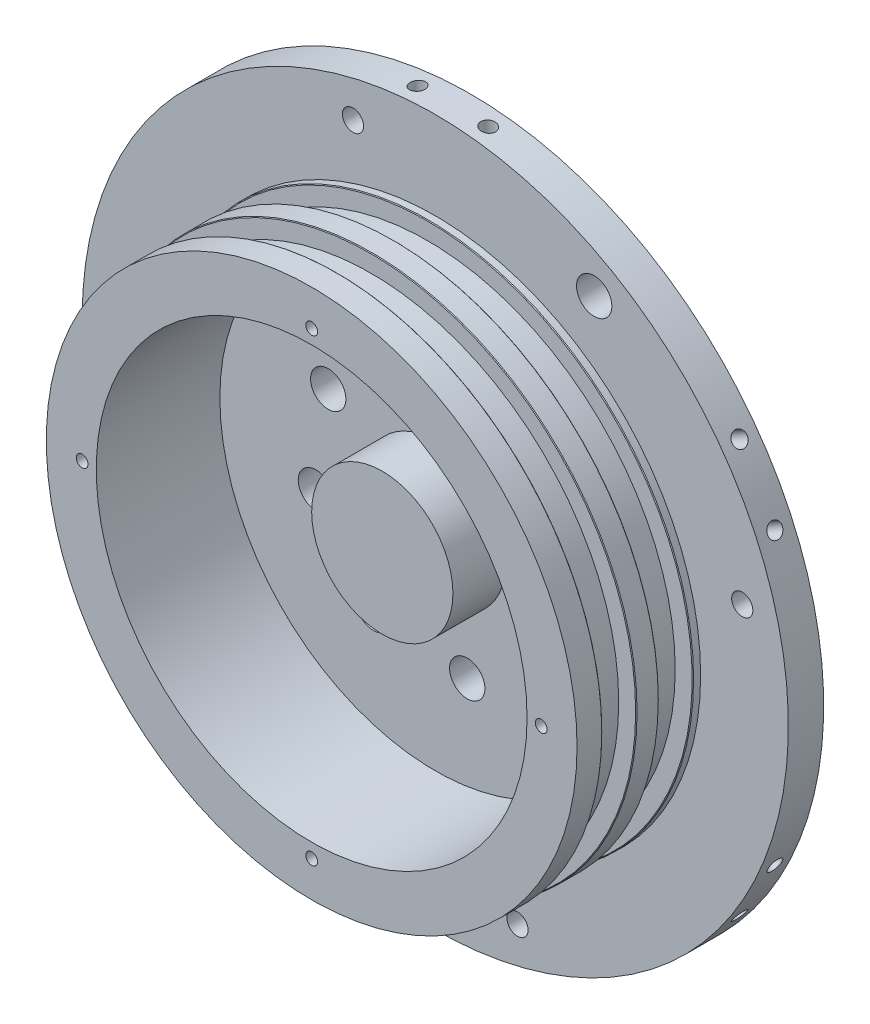
SolidWorks part; units mm, degrees
other "Marquage1"
sketch "Esquisse22" plane through (-100, 100, -114.225) normal (-0.6969, 0.6451, 0.3132) x (0.5706, 0.7634, -0.3027)
sketch "Esquisse26" plane through (-110, 110, -114.225) normal (-0.6969, 0.6451, 0.3132) x (0.5706, 0.7634, -0.3027)
sketch "Esquisse28" plane through (-110, 110, -114.225) normal (-0.6969, 0.6451, 0.3132) x (0.5706, 0.7634, -0.3027)
sketch "Esquisse31" plane through (-110, 110, -114.225) normal (-0.6969, 0.6451, 0.3132) x (0.5706, 0.7634, -0.3027)
sketch "Esquisse32" plane through (-100, 100, -114.225) normal (-0.6969, 0.6451, 0.3132) x (0.5706, 0.7634, -0.3027)
material "AISI 316 Barre d'acier inoxydable recuit (SS)"
ref_plane "Plan de face" through (0, 0, 0) normal (0, 0, 1) x (1, 0, 0)
ref_plane "Plan de dessus" through (0, 0, 0) normal (0, 1, 0) x (1, 0, 0)
ref_plane "Plan de droite" through (0, 0, 0) normal (1, 0, 0) x (0, 0, -1)
sketch "Esquisse1" plane through (0, 0, 0) normal (0, 1, 0) x (1, 0, 0)
  line L0 (87.5, 159.225) -> (0, 159.225)
  line L1 (0, 159.225) -> (0, 114.225)
  line L2 (0, 114.225) -> (75.15, 114.225)
  line L3 (75.15, 114.225) -> (75.15, 121.425)
  line L4 (75.15, 121.425) -> (70.15, 121.425)
  line L5 (70.15, 121.425) -> (70.15, 131.025)
  line L6 (70.15, 131.025) -> (75.15, 131.025)
  line L7 (75.15, 131.025) -> (75.15, 137.425)
  line L8 (75.15, 137.425) -> (70.15, 137.425)
  line L9 (70.15, 137.425) -> (70.15, 147.025)
  line L10 (70.15, 147.025) -> (75.15, 147.025)
  line L11 (75.15, 147.025) -> (75.15, 149.225)
  line L12 (75.15, 149.225) -> (87.5, 149.225)
  line L13 (87.5, 149.225) -> (87.5, 159.225)
  line L14 (0, 159.225) -> (0, 114.225) construction
revolve "Révolution1" add sketch "Esquisse1" angle 360 about L14 reverse direction yes
hole_wizard "Diamètre du perçage Ø9.0 (9)1" positions "Esquisse3" profile "Esquisse2" hole size "Ø9.0" standard "Ansi Metric"
sketch "Esquisse3" plane through (0, 0, -149.225) normal (0, 0, 1) x (1, 0, 0)
  point P0 (-87.5, 0)
  point P1 (0, 87.5)
  point P2 (0, -87.5)
  point P3 (87.5, 0)
sketch "Esquisse2" plane through (-87.5, 0, -149.225) normal (1, 0, 0) x (0, -1, 0)
  line L0 (0, 0) -> (0, 3)
  line L1 (0, 3) -> (4.5, 3)
  line L2 (4.5, 3) -> (4.5, 0)
  line L5 (4.5, 0) -> (0, 0)
  line L10 (0, 3) -> (-4.5, 3) construction
  line L11 (0, -6.35) -> (0, 107.95) construction
  dimension "Diamètre du perçage" = 9
  dimension "Profondeur du perçage" = 3
  dimension "Angle de pointe" = 180
hole_wizard "Dégagement M31" positions "Esquisse5" profile "Esquisse4" hole size "M3" standard "Ansi Metric"
sketch "Esquisse5" plane through (0, 0, -114.225) normal (0, 0, 1) x (1, 0, 0)
  point P0 (-65, 0)
  point P1 (65, 0)
  point P2 (0, 65)
  point P3 (0, -65)
sketch "Esquisse4" plane through (-65, 0, -114.225) normal (1, 0, 0) x (0, -1, 0)
  line L0 (0, 0) -> (0, 17.001)
  line L1 (0, 17.001) -> (1.666, 16)
  line L2 (1.666, 16) -> (1.666, 0)
  line L5 (1.666, 0) -> (0, 0)
  line L10 (0, 17.001) -> (-1.666, 16) construction
  line L11 (0, -6.35) -> (0, 107.95) construction
  dimension "Diamètre du perçage" = 3.332
  dimension "Profondeur du perçage" = 16
  dimension "Angle de pointe" = 118
hole_wizard "Dégagement M1001" positions "Esquisse7" profile "Esquisse6" hole size "M100" standard "Ansi Metric"
sketch "Esquisse7" plane through (0, 0, -114.225) normal (0, 0, 1) x (1, 0, 0)
  point P0 (0, 0)
sketch "Esquisse6" plane through (0, 0, -114.225) normal (1, 0, 0) x (0, -1, 0)
  line L0 (0, 0) -> (0, 35)
  line L1 (0, 35) -> (55, 35)
  line L2 (55, 35) -> (55, 0)
  line L5 (55, 0) -> (0, 0)
  line L10 (0, 35) -> (-55, 35) construction
  line L11 (0, -6.35) -> (0, 107.95) construction
  dimension "Diamètre du perçage" = 110
  dimension "Profondeur du perçage" = 35
  dimension "Angle de pointe" = 180
sketch "Esquisse8" plane through (0, 0, -159.225) normal (0, 0, -1) x (-1, 0, 0)
  line L0 (0, 0) -> (0, -108.9201) construction
  circle A0 centre (0, 0) radius 108.9201 construction
  circle A1 centre (0, 0) radius 100
  circle A2 centre (0, 0) radius 77.5
  circle A3 centre (0, 0) radius 87.5 construction
  dimension "D2" = 10
  dimension "D1" = 200
extrude "Boss.-Extru.1" add sketch "Esquisse8" against normal blind 10
sketch "Esquisse9" plane through (0, 0, -159.225) normal (0, 0, 1) x (1, 0, 0)
  line L0 (0, -65) -> (0, 0) construction
  line L1 (-56.2917, -32.5) -> (0, -65) construction
  line L2 (-56.2917, -32.5) -> (0, 0) construction
  line L3 (0, 0) -> (-28.1458, -48.75) construction
  circle A0 centre (0, -65) radius 2.5
  circle A3 centre (-56.2917, -32.5) radius 2.5
  circle A4 centre (-56.2917, 32.5) radius 2.5
  circle A5 centre (0, 65) radius 2.5
  circle A6 centre (56.2917, 32.5) radius 2.5
  circle A7 centre (56.2917, -32.5) radius 2.5
  point P31 (0, 0)
  dimension "D1" = 5
  dimension "D2" = 65
  dimension "D3" = 6
extrude "Enlèv. mat.-Extru.1" cut sketch "Esquisse9" along normal blind 20
ref_plane "Plan1" through (0, -100, 0) normal (0, -1, 0) x (-1, 0, 0)
sketch "Esquisse10" plane through (0, -100, 0) normal (0, -1, 0) x (1, 0, 0)
  line L0 (0, -159.225) -> (0, -149.225) construction
  line L2 (-100, -159.225) -> (100, -159.225) construction
  line L3 (100, -149.225) -> (-100, -149.225) construction
  circle A3 centre (10, -154.225) radius 2.1
  circle A4 centre (-10, -154.225) radius 2.1
  dimension "D1" = 4.2
  dimension "D2" = 5
  dimension "D3" = 20
extrude "Enlèv. mat.-Extru.2" cut sketch "Esquisse10" against normal blind 25
pattern_circular "Répétition circulaire1" count 6 every 60 about axis through (0, 0, -121.425) along (0, 0, 1) of "Enlèv. mat.-Extru.2"
sketch "Esquisse24" plane through (0, 0, -159.225) normal (0, 0, -1) x (-1, 0, 0)
  line L0 (28.0621, 104.7291) -> (0, 0) construction
  line L1 (-54.2118, 93.8976) -> (0, 0) construction
  line L2 (0, 0) -> (0, 65) construction
  circle A0 centre (-45, 77.9423) radius 5
  circle A1 centre (23.2937, 86.9333) radius 3
  circle A2 centre (86.9333, -23.2937) radius 3
  circle A3 centre (-23.2937, -86.9333) radius 3
  circle A4 centre (-86.9333, 23.2937) radius 3
  circle A5 centre (-17.5, 30.3109) radius 5
  circle A6 centre (9.0587, 33.8074) radius 5
  circle A7 centre (30.3109, 17.5) radius 5
  circle A8 centre (33.8074, -9.0587) radius 5
  circle A9 centre (17.5, -30.3109) radius 5
  circle A10 centre (-9.0587, -33.8074) radius 5
  circle A11 centre (-30.3109, -17.5) radius 5
  circle A12 centre (-33.8074, 9.0587) radius 5
  point P19 (0, 0)
  point P36 (0, 0)
  dimension "D1" = 6
  dimension "D3" = 10
  dimension "D6" = 10
  dimension "D2" = 90
  dimension "D4" = 90
  dimension "D7" = 35
  dimension "D9" = 45
  dimension "D10" = 15
  dimension "D5" = 4
  dimension "D8" = 8
extrude "Enlèv. mat.-Extru.15" cut sketch "Esquisse24" against normal through all and the other way through all
sketch "Esquisse27" plane through (0, 0, -114.225) normal (0, 0, 1) x (1, 0, 0)
  circle A0 centre (0, 0) radius 62.15
  circle A1 centre (0, 0) radius 70.15 construction
  circle A2 centre (0, 0) radius 70.15 construction
  dimension "D1" = 8
chamfer "Chanfrein1" distance 0.2 angle 45 4 edges at (75.15, 0, -147.025) (75.15, 0, -121.425) (75.15, 0, -131.025) (75.15, 0, -137.425)
sketch "Esquisse25" plane through (0, 0, -159.225) normal (0, 0, -1) x (-1, 0, 0)
  line L0 (-31.6901, 0.1056) -> (-40.1175, 2.3637) construction
  line L1 (-40.1175, 2.3637) -> (-35.9247, 18.0117) construction
  line L2 (-35.9247, 18.0117) -> (-27.4973, 15.7536) construction
  line L3 (-27.4973, 15.7536) -> (-31.6901, 0.1056) construction
  line L4 (0, 0) -> (-38.0211, 10.1877) construction
  line L5 (-33.8074, 9.0587) -> (-40.6755, -16.5735) construction
  line L6 (-29.2962, 16.2356) -> (-34.1258, 17.5297)
  line L7 (-33.489, 0.5876) -> (-38.3187, 1.8817)
  line L8 (-9.2352, 32.1958) -> (-11.7352, 36.526)
  line L9 (-23.2648, 24.0958) -> (-25.7648, 28.426)
  line L10 (16.2356, 29.2962) -> (17.5297, 34.1258)
  line L11 (0.5876, 33.489) -> (1.8817, 38.3187)
  line L12 (32.1958, 9.2352) -> (36.526, 11.7352)
  line L13 (24.0958, 23.2648) -> (28.426, 25.7648)
  line L14 (29.2962, -16.2356) -> (34.1258, -17.5297)
  line L15 (33.489, -0.5876) -> (38.3187, -1.8817)
  line L16 (9.2352, -32.1958) -> (11.7352, -36.526)
  line L17 (23.2648, -24.0958) -> (25.7648, -28.426)
  line L18 (-16.2356, -29.2962) -> (-17.5297, -34.1258)
  line L19 (-0.5876, -33.489) -> (-1.8817, -38.3187)
  line L20 (-32.1958, -9.2352) -> (-36.526, -11.7352)
  line L21 (-24.0958, -23.2648) -> (-28.426, -25.7648)
  arc A2 (-40.1175, 2.3637) -> (-35.9247, 18.0117) centre (-33.8074, 9.0587) cw construction
  arc A3 (-31.6901, 0.1056) -> (-27.4973, 15.7536) centre (-33.8074, 9.0587) ccw construction
  arc A4 (-29.5648, 0.8953) -> (-26.0515, 14.007) centre (-33.8074, 9.0587) ccw
  arc A5 (-26.0515, 14.007) -> (-26.2567, 14.3863) centre (-23.5224, 15.6206) cw
  arc A6 (-26.2567, 14.3863) -> (-28.7554, 16.1427) centre (-28.991, 13.1519) ccw
  arc A7 (-28.7554, 16.1427) -> (-29.2962, 16.2356) centre (-28.5197, 19.1334) cw
  arc A8 (-34.6406, 17.7196) -> (-34.1258, 17.5297) centre (-33.3493, 20.4275) ccw
  arc A9 (-37.6827, 17.4479) -> (-34.6406, 17.7196) centre (-35.9319, 15.0117) cw
  arc A10 (-38.05, 17.222) -> (-37.6827, 17.4479) centre (-39.4335, 19.884) ccw
  arc A11 (-41.5633, 4.1103) -> (-38.05, 17.222) centre (-33.8074, 9.0587) cw
  arc A12 (-41.5633, 4.1103) -> (-41.3581, 3.7311) centre (-44.0924, 2.4967) cw
  arc A13 (-41.3581, 3.7311) -> (-38.8594, 1.9747) centre (-38.6238, 4.9654) ccw
  arc A14 (-38.8594, 1.9747) -> (-38.3187, 1.8817) centre (-39.0951, -1.0161) cw
  arc A15 (-32.9742, 0.3977) -> (-33.489, 0.5876) centre (-34.2655, -2.3102) ccw
  arc A16 (-29.9321, 0.6695) -> (-32.9742, 0.3977) centre (-31.6829, 3.1056) cw
  arc A17 (-29.5648, 0.8953) -> (-29.9321, 0.6695) centre (-28.1813, -1.7666) ccw
  arc A19 (-26.4833, 32.2961) -> (-14.7276, 39.0832) centre (-17.5, 30.3109) cw
  arc A20 (-14.7276, 39.0832) -> (-14.3082, 38.9832) centre (-13.8236, 41.9438) ccw
  arc A21 (-14.3082, 38.9832) -> (-11.9649, 37.0243) centre (-14.7928, 36.0226) cw
  arc A22 (-11.9649, 37.0243) -> (-11.7352, 36.526) centre (-9.1371, 38.026) ccw
  arc A23 (-8.9185, 31.7477) -> (-9.2352, 32.1958) centre (-6.6371, 33.6958) cw
  arc A24 (-8.3937, 28.7389) -> (-8.9185, 31.7477) centre (-11.1999, 29.7996) ccw
  arc A25 (-8.5167, 28.3257) -> (-8.3937, 28.7389) centre (-5.5874, 27.6783) cw
  arc A26 (-20.2724, 21.5386) -> (-8.5167, 28.3257) centre (-17.5, 30.3109) ccw
  arc A27 (-20.2724, 21.5386) -> (-20.6918, 21.6386) centre (-21.1764, 18.678) ccw
  arc A28 (-20.6918, 21.6386) -> (-23.0351, 23.5975) centre (-20.2072, 24.5992) cw
  arc A29 (-23.0351, 23.5975) -> (-23.2648, 24.0958) centre (-25.8629, 22.5958) ccw
  arc A30 (-26.0815, 28.8741) -> (-25.7648, 28.426) centre (-28.3629, 26.926) cw
  arc A31 (-26.6063, 31.8828) -> (-26.0815, 28.8741) centre (-23.8001, 30.8222) ccw
  arc A32 (-26.4833, 32.2961) -> (-26.6063, 31.8828) centre (-29.4126, 32.9435) cw
  arc A33 (4.1103, 41.5633) -> (17.222, 38.05) centre (9.0587, 33.8074) cw
  arc A34 (17.222, 38.05) -> (17.4479, 37.6827) centre (19.884, 39.4335) ccw
  arc A35 (17.4479, 37.6827) -> (17.7196, 34.6406) centre (15.0117, 35.9319) cw
  arc A36 (17.7196, 34.6406) -> (17.5297, 34.1258) centre (20.4275, 33.3493) ccw
  arc A37 (16.1427, 28.7554) -> (16.2356, 29.2962) centre (19.1334, 28.5197) cw
  arc A38 (14.3863, 26.2567) -> (16.1427, 28.7554) centre (13.1519, 28.991) ccw
  arc A39 (14.007, 26.0515) -> (14.3863, 26.2567) centre (15.6206, 23.5224) cw
  arc A40 (0.8953, 29.5648) -> (14.007, 26.0515) centre (9.0587, 33.8074) ccw
  arc A41 (0.8953, 29.5648) -> (0.6695, 29.9321) centre (-1.7666, 28.1813) ccw
  arc A42 (0.6695, 29.9321) -> (0.3977, 32.9742) centre (3.1056, 31.6829) cw
  arc A43 (0.3977, 32.9742) -> (0.5876, 33.489) centre (-2.3102, 34.2655) ccw
  arc A44 (1.9747, 38.8594) -> (1.8817, 38.3187) centre (-1.0161, 39.0951) cw
  arc A45 (3.7311, 41.3581) -> (1.9747, 38.8594) centre (4.9654, 38.6238) ccw
  arc A46 (4.1103, 41.5633) -> (3.7311, 41.3581) centre (2.4967, 44.0924) cw
  arc A47 (32.2961, 26.4833) -> (39.0832, 14.7276) centre (30.3109, 17.5) cw
  arc A48 (39.0832, 14.7276) -> (38.9832, 14.3082) centre (41.9438, 13.8236) ccw
  arc A49 (38.9832, 14.3082) -> (37.0243, 11.9649) centre (36.0226, 14.7928) cw
  arc A50 (37.0243, 11.9649) -> (36.526, 11.7352) centre (38.026, 9.1371) ccw
  arc A51 (31.7477, 8.9185) -> (32.1958, 9.2352) centre (33.6958, 6.6371) cw
  arc A52 (28.7389, 8.3937) -> (31.7477, 8.9185) centre (29.7996, 11.1999) ccw
  arc A53 (28.3257, 8.5167) -> (28.7389, 8.3937) centre (27.6783, 5.5874) cw
  arc A54 (21.5386, 20.2724) -> (28.3257, 8.5167) centre (30.3109, 17.5) ccw
  arc A55 (21.5386, 20.2724) -> (21.6386, 20.6918) centre (18.678, 21.1764) ccw
  arc A56 (21.6386, 20.6918) -> (23.5975, 23.0351) centre (24.5992, 20.2072) cw
  arc A57 (23.5975, 23.0351) -> (24.0958, 23.2648) centre (22.5958, 25.8629) ccw
  arc A58 (28.8741, 26.0815) -> (28.426, 25.7648) centre (26.926, 28.3629) cw
  arc A59 (31.8828, 26.6063) -> (28.8741, 26.0815) centre (30.8222, 23.8001) ccw
  arc A60 (32.2961, 26.4833) -> (31.8828, 26.6063) centre (32.9435, 29.4126) cw
  arc A61 (41.5633, -4.1103) -> (38.05, -17.222) centre (33.8074, -9.0587) cw
  arc A62 (38.05, -17.222) -> (37.6827, -17.4479) centre (39.4335, -19.884) ccw
  arc A63 (37.6827, -17.4479) -> (34.6406, -17.7196) centre (35.9319, -15.0117) cw
  arc A64 (34.6406, -17.7196) -> (34.1258, -17.5297) centre (33.3493, -20.4275) ccw
  arc A65 (28.7554, -16.1427) -> (29.2962, -16.2356) centre (28.5197, -19.1334) cw
  arc A66 (26.2567, -14.3863) -> (28.7554, -16.1427) centre (28.991, -13.1519) ccw
  arc A67 (26.0515, -14.007) -> (26.2567, -14.3863) centre (23.5224, -15.6206) cw
  arc A68 (29.5648, -0.8953) -> (26.0515, -14.007) centre (33.8074, -9.0587) ccw
  arc A69 (29.5648, -0.8953) -> (29.9321, -0.6695) centre (28.1813, 1.7666) ccw
  arc A70 (29.9321, -0.6695) -> (32.9742, -0.3977) centre (31.6829, -3.1056) cw
  arc A71 (32.9742, -0.3977) -> (33.489, -0.5876) centre (34.2655, 2.3102) ccw
  arc A72 (38.8594, -1.9747) -> (38.3187, -1.8817) centre (39.0951, 1.0161) cw
  arc A73 (41.3581, -3.7311) -> (38.8594, -1.9747) centre (38.6238, -4.9654) ccw
  arc A74 (41.5633, -4.1103) -> (41.3581, -3.7311) centre (44.0924, -2.4967) cw
  arc A75 (26.4833, -32.2961) -> (14.7276, -39.0832) centre (17.5, -30.3109) cw
  arc A76 (14.7276, -39.0832) -> (14.3082, -38.9832) centre (13.8236, -41.9438) ccw
  arc A77 (14.3082, -38.9832) -> (11.9649, -37.0243) centre (14.7928, -36.0226) cw
  arc A78 (11.9649, -37.0243) -> (11.7352, -36.526) centre (9.1371, -38.026) ccw
  arc A79 (8.9185, -31.7477) -> (9.2352, -32.1958) centre (6.6371, -33.6958) cw
  arc A80 (8.3937, -28.7389) -> (8.9185, -31.7477) centre (11.1999, -29.7996) ccw
  arc A81 (8.5167, -28.3257) -> (8.3937, -28.7389) centre (5.5874, -27.6783) cw
  arc A82 (20.2724, -21.5386) -> (8.5167, -28.3257) centre (17.5, -30.3109) ccw
  arc A83 (20.2724, -21.5386) -> (20.6918, -21.6386) centre (21.1764, -18.678) ccw
  arc A84 (20.6918, -21.6386) -> (23.0351, -23.5975) centre (20.2072, -24.5992) cw
  arc A85 (23.0351, -23.5975) -> (23.2648, -24.0958) centre (25.8629, -22.5958) ccw
  arc A86 (26.0815, -28.8741) -> (25.7648, -28.426) centre (28.3629, -26.926) cw
  arc A87 (26.6063, -31.8828) -> (26.0815, -28.8741) centre (23.8001, -30.8222) ccw
  arc A88 (26.4833, -32.2961) -> (26.6063, -31.8828) centre (29.4126, -32.9435) cw
  arc A89 (-4.1103, -41.5633) -> (-17.222, -38.05) centre (-9.0587, -33.8074) cw
  arc A90 (-17.222, -38.05) -> (-17.4479, -37.6827) centre (-19.884, -39.4335) ccw
  arc A91 (-17.4479, -37.6827) -> (-17.7196, -34.6406) centre (-15.0117, -35.9319) cw
  arc A92 (-17.7196, -34.6406) -> (-17.5297, -34.1258) centre (-20.4275, -33.3493) ccw
  arc A93 (-16.1427, -28.7554) -> (-16.2356, -29.2962) centre (-19.1334, -28.5197) cw
  arc A94 (-14.3863, -26.2567) -> (-16.1427, -28.7554) centre (-13.1519, -28.991) ccw
  arc A95 (-14.007, -26.0515) -> (-14.3863, -26.2567) centre (-15.6206, -23.5224) cw
  arc A96 (-0.8953, -29.5648) -> (-14.007, -26.0515) centre (-9.0587, -33.8074) ccw
  arc A97 (-0.8953, -29.5648) -> (-0.6695, -29.9321) centre (1.7666, -28.1813) ccw
  arc A98 (-0.6695, -29.9321) -> (-0.3977, -32.9742) centre (-3.1056, -31.6829) cw
  arc A99 (-0.3977, -32.9742) -> (-0.5876, -33.489) centre (2.3102, -34.2655) ccw
  arc A100 (-1.9747, -38.8594) -> (-1.8817, -38.3187) centre (1.0161, -39.0951) cw
  arc A101 (-3.7311, -41.3581) -> (-1.9747, -38.8594) centre (-4.9654, -38.6238) ccw
  arc A102 (-4.1103, -41.5633) -> (-3.7311, -41.3581) centre (-2.4967, -44.0924) cw
  arc A103 (-32.2961, -26.4833) -> (-39.0832, -14.7276) centre (-30.3109, -17.5) cw
  arc A104 (-39.0832, -14.7276) -> (-38.9832, -14.3082) centre (-41.9438, -13.8236) ccw
  arc A105 (-38.9832, -14.3082) -> (-37.0243, -11.9649) centre (-36.0226, -14.7928) cw
  arc A106 (-37.0243, -11.9649) -> (-36.526, -11.7352) centre (-38.026, -9.1371) ccw
  arc A107 (-31.7477, -8.9185) -> (-32.1958, -9.2352) centre (-33.6958, -6.6371) cw
  arc A108 (-28.7389, -8.3937) -> (-31.7477, -8.9185) centre (-29.7996, -11.1999) ccw
  arc A109 (-28.3257, -8.5167) -> (-28.7389, -8.3937) centre (-27.6783, -5.5874) cw
  arc A110 (-21.5386, -20.2724) -> (-28.3257, -8.5167) centre (-30.3109, -17.5) ccw
  arc A111 (-21.5386, -20.2724) -> (-21.6386, -20.6918) centre (-18.678, -21.1764) ccw
  arc A112 (-21.6386, -20.6918) -> (-23.5975, -23.0351) centre (-24.5992, -20.2072) cw
  arc A113 (-23.5975, -23.0351) -> (-24.0958, -23.2648) centre (-22.5958, -25.8629) ccw
  arc A114 (-28.8741, -26.0815) -> (-28.426, -25.7648) centre (-26.926, -28.3629) cw
  arc A115 (-31.8828, -26.6063) -> (-28.8741, -26.0815) centre (-30.8222, -23.8001) ccw
  arc A116 (-32.2961, -26.4833) -> (-31.8828, -26.6063) centre (-32.9435, -29.4126) cw
  point P7 (-29.5937, 7.9296)
  point P35 (-31.711, 16.8827)
  point P250 (0, 0)
  dimension "D1" = 9.2
  dimension "D3" = 3
  dimension "D4" = 2.5
  dimension "D2" = 16.2
  dimension "D5" = 8
sketch "Esquisse29" plane through (0, 0, -159.225) normal (0, 0, 1) x (1, 0, 0)
  circle A0 centre (0, 0) radius 20
  dimension "D1" = 40
extrude "Boss.-Extru.3" add sketch "Esquisse29" along normal blind 25
sketch "Esquisse30" plane through (0, 0, -159.225) normal (0, 0, 1) x (1, 0, 0)
  line L0 (0, 0) -> (0, 16.7478) construction
  line L1 (0, 0) -> (-20, 0) construction
  circle A0 centre (0, 0) radius 20 construction
  circle A1 centre (-15, 0) radius 2.5
  circle A2 centre (0, 15) radius 2.5
  circle A3 centre (15, 0) radius 2.5
  circle A4 centre (0, -15) radius 2.5
  point P18 (0, 0)
  dimension "D1" = 4
  dimension "D3" = 5
  dimension "D2" = 15
extrude "Enlèv. mat.-Extru.17" cut sketch "Esquisse30" along normal blind 15
extrude "Enlèv. mat.-Extru.18" cut sketch "Esquisse25" against normal blind 2
sketch "Esquisse34" plane through (0, 0, -114.225) normal (0, 0, 1) x (1, 0, 0)
  circle A0 centre (0, 0) radius 20
  circle A1 centre (0, 0) radius 61
  circle A2 centre (0, 0) radius 20 construction
  dimension "D1" = 122
extrude "Enlèv. mat.-Extru.19" cut sketch "Esquisse34" against normal up to surface (35 mm away) up to face at (-20, 0, -149.225)
